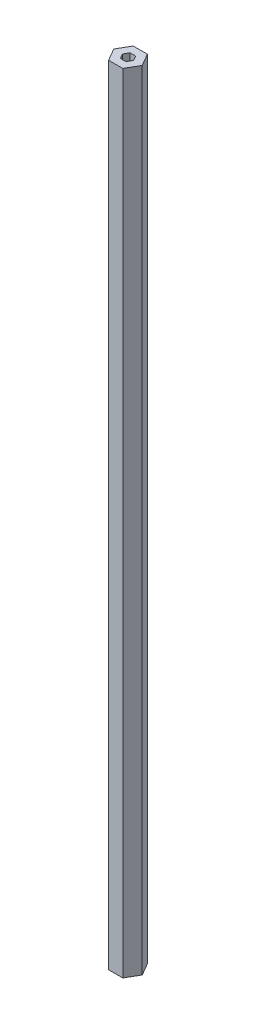
SolidWorks part; units mm, degrees
ref_plane "Front Plane" through (0, 0, 0) normal (0, 0, 1) x (1, 0, 0)
ref_plane "Top Plane" through (0, 0, 0) normal (0, 1, 0) x (1, 0, 0)
ref_plane "Right Plane" through (0, 0, 0) normal (1, 0, 0) x (0, 0, -1)
sketch "Sketch1" plane through (0, 0, 0) normal (0, 1, 0) x (1, 0, 0)
  line L9 (7.3323, 0) -> (3.6662, 6.35)
  line L10 (3.6662, 6.35) -> (-3.6662, 6.35)
  line L11 (-3.6662, 6.35) -> (-7.3323, 0)
  line L12 (-7.3323, 0) -> (-3.6662, -6.35)
  line L13 (-3.6662, -6.35) -> (3.6662, -6.35)
  line L14 (3.6662, -6.35) -> (7.3323, 0)
  line L15 (1.4434, 2.5) -> (-1.4434, 2.5)
  line L16 (-1.4434, 2.5) -> (-2.8868, 0)
  line L17 (-2.8868, 0) -> (-1.4434, -2.5)
  line L18 (-1.4434, -2.5) -> (1.4434, -2.5)
  line L19 (1.4434, -2.5) -> (2.8868, 0)
  line L20 (2.8868, 0) -> (1.4434, 2.5)
  circle A0 centre (0, 0) radius 6.35 construction
  circle A1 centre (0, 0) radius 2.5 construction
  dimension "D1" = 12.7
  dimension "D2" = 5
extrude "Boss-Extrude1" add sketch "Sketch1" along normal blind 406.4
